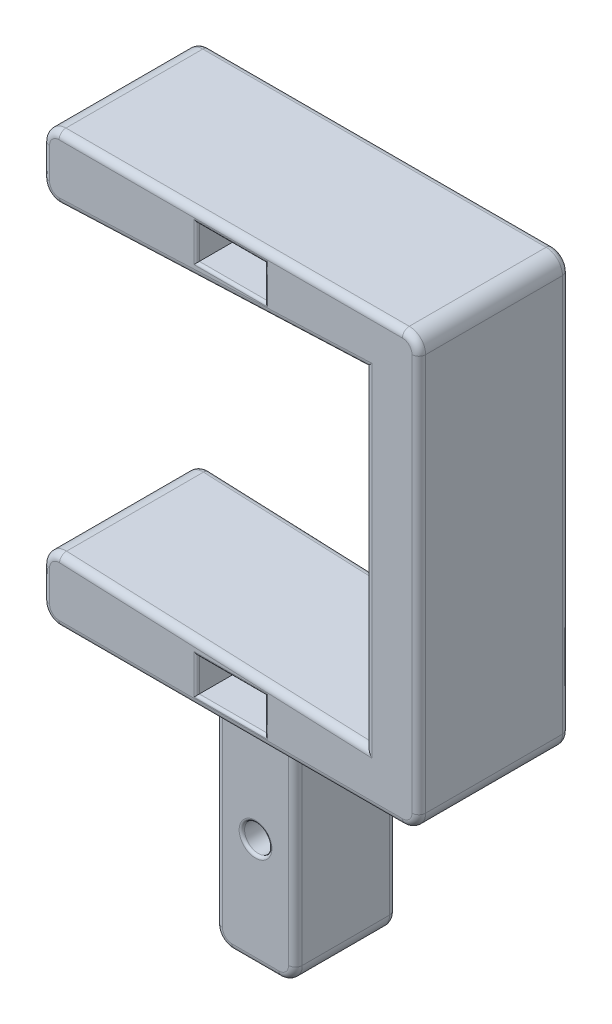
SolidWorks part; units mm, degrees
ref_plane "Front Plane" through (0, 0, 0) normal (0, 0, 1) x (1, 0, 0)
ref_plane "Top Plane" through (0, 0, 0) normal (0, 1, 0) x (1, 0, 0)
ref_plane "Right Plane" through (0, 0, 0) normal (1, 0, 0) x (0, 0, -1)
sketch "Sketch1" plane through (0, 0, 0) normal (0, 0, 1) x (1, 0, 0)
  line L0 (-35, 4.4112) -> (-35, 1.524)
  line L2 (0, 1.524) -> (0, 38.476)
  line L5 (-33.476, 40) -> (-1.524, 40)
  line L6 (-35, 38.476) -> (-35, 35.5888)
  line L7 (-33.476, 0) -> (-1.524, 0)
  line L8 (-5, 35.25) -> (-5, 4.75)
  line L12 (-5, 35.25) -> (-5, 4.75)
  line L13 (-5, 4.75) -> (-5, 35.25)
  line L15 (-5, 35.25) -> (-33.4126, 34.0661)
  line L16 (-5, 4.75) -> (-33.4126, 5.9339)
  line L18 (-5, 20) -> (-81.153, 20) construction
  arc A0 (-33.4126, 34.0661) -> (-35, 35.5888) centre (-33.476, 35.5888) cw
  arc A1 (-33.4126, 5.9339) -> (-35, 4.4112) centre (-33.476, 4.4112) ccw
  arc A2 (-35, 1.524) -> (-33.476, 0) centre (-33.476, 1.524) ccw
  arc A3 (-1.524, 0) -> (0, 1.524) centre (-1.524, 1.524) ccw
  arc A4 (0, 38.476) -> (-1.524, 40) centre (-1.524, 38.476) ccw
  arc A5 (-33.476, 40) -> (-35, 38.476) centre (-33.476, 38.476) ccw
  point P23 (-35, 34)
  point P26 (-35, 6)
  point P31 (0, 0)
  dimension "D6" = 1.524
  dimension "D1" = 30.5
  dimension "D2" = 28
  dimension "D3" = 30
  dimension "D4" = 40
  dimension "D5" = 5
extrude "Boss-Extrude1" add sketch "Sketch1" along normal blind 7 and the other way blind 7 contours L5 A5 L6 A0 L15 L8 L13 L16 A1 L0 A2 L7 A3 L2 A4 region at (-34.163, 5.1274, 0)
sketch "Sketch2" plane through (0, 0, 0) normal (0, 0, 1) x (1, 0, 0)
  line L0 (-33.476, 0) -> (-1.524, 0) construction
  line L1 (-21.2147, 0) -> (-13.7852, 0)
  line L2 (-21.2147, 0) -> (-21.2147, -18.796)
  line L3 (-19.6907, -20.32) -> (-15.3092, -20.32)
  line L4 (-13.7852, 0) -> (-13.7852, -18.796)
  line L5 (-17.5, 0) -> (-17.5, -20.32) construction
  arc A0 (-15.3092, -20.32) -> (-13.7852, -18.796) centre (-15.3092, -18.796) ccw
  arc A1 (-21.2147, -18.796) -> (-19.6907, -20.32) centre (-19.6907, -18.796) ccw
  circle A2 centre (-17.5, -10.16) radius 1.27
  point P13 (-17.5, 0)
  dimension "D3" = 1.524
  dimension "D5" = 2.54
  dimension "D1" = 7.4295
  dimension "D2" = 20.32
  dimension "D4" = 10.16
extrude "Boss-Extrude2" add sketch "Sketch2" along normal blind 4.699 and the other way blind 4.699
fillet "Fillet2" radius 0.635 38 edges at (-21.2147, -9.398, -4.699) (-20.7684, -19.8736, -4.699) (-17.5, -20.32, -4.699) (-14.2316, -19.8736, -4.699) (-21.2147, -9.398, 4.699) (-20.7684, -19.8736, 4.699) (-17.5, -20.32, 4.699) (-14.2316, -19.8736, 4.699) (-19.2063, 5.3419, -7) (-34.531, 5.511, -7) (-35, 2.9676, -7) (-34.5536, 0.4464, -7) (-17.5, 0, -7) (-0.4464, 0.4464, -7) (-19.2063, 34.6581, -7) (-34.531, 34.489, -7) (-35, 37.0324, -7) (-34.5536, 39.5536, -7) (-17.5, 40, -7) (-0.4464, 39.5536, -7) (-19.2063, 5.3419, 7) (-34.531, 5.511, 7) (-35, 2.9676, 7) (-34.5536, 0.4464, 7) (-17.5, 0, 7) (-0.4464, 0.4464, 7) (-19.2063, 34.6581, 7) (-34.531, 34.489, 7) (-35, 37.0324, 7) (-34.5536, 39.5536, 7) (-17.5, 40, 7) (-0.4464, 39.5536, 7) (-5, 20, 7) (-5, 20, -7) (-13.7852, -9.398, -4.699) (-13.7852, -9.398, 4.699) (0, 20, -7) (0, 20, 7)
sketch "Sketch3" plane through (0, 0, 0) normal (0, 0, 1) x (1, 0, 0)
  line L1 (-14.325, 0.9818) -> (-20.675, 0.9818)
  line L2 (-14.325, 0.9818) -> (-14.325, 4.1568)
  line L3 (-14.325, 4.1568) -> (-20.675, 4.1568)
  line L4 (-20.675, 0.9818) -> (-20.675, 4.1568)
  line L9 (-14.4202, 0) -> (-20.5797, 0) construction
  line L11 (-20.675, 39.0182) -> (-14.325, 39.0182)
  line L12 (-20.675, 39.0182) -> (-20.675, 35.8432)
  line L13 (-20.675, 35.8432) -> (-14.325, 35.8432)
  line L14 (-14.325, 39.0182) -> (-14.325, 35.8432)
  line L15 (-14.325, 40) -> (-14.325, 34.8615) construction
  line L16 (-33.476, 40) -> (-1.524, 40) construction
  line L17 (-5, 35.25) -> (-33.4126, 34.0661) construction
  line L18 (-4.365, 20) -> (-34.9842, 20) construction
  line L19 (-4.365, 35.912) -> (-4.365, 4.088) construction
  point P4 (-14.325, 37.4307)
  point P10 (-14.325, 37.4307)
  point P15 (-17.5, 0)
  point P16 (-17.5, 0.9818)
  dimension "D1" = 3.175
  dimension "D2" = 6.35
  dimension "D3" = 3.175
  dimension "D4" = 6.35
extrude "Cut-Extrude1" cut sketch "Sketch3" against normal through all and the other way through all
fillet "Fillet3" radius 0.254 18 edges at (-20.675, 2.5693, -7) (-14.325, 2.5693, -7) (-14.325, 2.5693, 7) (-20.675, 2.5693, 7) (-14.325, 37.4307, -7) (-20.675, 37.4307, -7) (-14.325, 37.4307, 7) (-20.675, 37.4307, 7) (-17.5, 0.9818, 7) (-17.5, 0.9818, -7) (-17.5, 4.1568, -7) (-17.5, 4.1568, 7) (-17.5, 35.8432, -7) (-17.5, 39.0182, -7) (-17.5, 39.0182, 7) (-17.5, 35.8432, 7) (-16.23, -10.16, 4.699) (-16.23, -10.16, -4.699)
